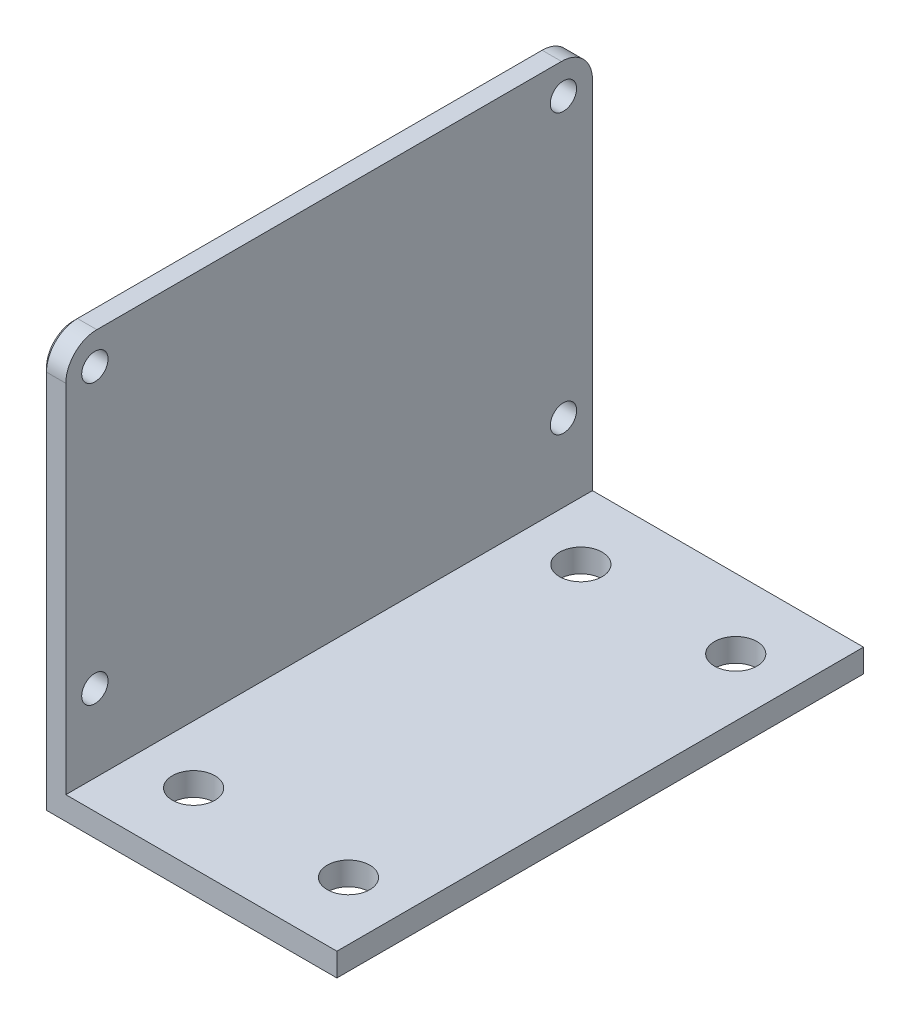
SolidWorks part; units mm, degrees
material "6061-T6 (SS)"
ref_plane "Front Plane" through (0, 0, 0) normal (0, 0, 1) x (1, 0, 0)
ref_plane "Top Plane" through (0, 0, 0) normal (0, 1, 0) x (1, 0, 0)
ref_plane "Right Plane" through (0, 0, 0) normal (1, 0, 0) x (0, 0, -1)
sketch "Sketch1" plane through (0, 0, 0) normal (0, 0, 1) x (1, 0, 0)
  line L0 (0, 0) -> (38, 0)
  line L1 (38, 0) -> (38, 3)
  line L2 (38, 3) -> (3, 3)
  line L3 (3, 3) -> (3, 53)
  line L4 (3, 53) -> (0, 53)
  line L5 (0, 53) -> (0, 0)
  dimension "D1" = 50
  dimension "D2" = 35
  dimension "D3" = 3
extrude "Boss-Extrude1" add sketch "Sketch1" along normal blind 68
sketch "Sketch2" plane through (3, 0, 0) normal (1, 0, 0) x (0, 0, -1)
  line L0 (-34, 31) -> (-34, 53) construction
  line L1 (-64.25, 49) -> (-3.75, 49) construction
  line L2 (-64.25, 49) -> (-64.25, 13) construction
  line L3 (-64.25, 13) -> (-3.75, 13) construction
  line L4 (-3.75, 49) -> (-3.75, 13) construction
  line L5 (-64.25, 49) -> (-3.75, 13) construction
  line L6 (-64.25, 13) -> (-3.75, 49) construction
  line L7 (-68, 53) -> (0, 53) construction
  point P0 (-34, 31)
  dimension "D1" = 60.5
  dimension "D2" = 36
  dimension "D3" = 4
hole_wizard "M3 Clearance Hole1" positions "Sketch4" profile "Sketch3" hole size "M3" standard "ANSI Metric"
sketch "Sketch4" plane through (3, 0, 0) normal (1, 0, 0) x (0, 0, -1)
  point P0 (-64.25, 49)
  point P3 (-3.75, 49)
  point P6 (-3.75, 13)
  point P9 (-64.25, 13)
sketch "Sketch3" plane through (3, 49, 64.25) normal (0, 1, 0) x (0, 0, -1)
  line L0 (0, 0) -> (0, 6.0215)
  line L1 (0, 6.0215) -> (1.7, 5)
  line L2 (1.7, 5) -> (1.7, 0)
  line L5 (1.7, 0) -> (0, 0)
  line L10 (0, 6.0215) -> (-1.7, 5) construction
  line L11 (0, -6.35) -> (0, 107.95) construction
  dimension "Hole Dia." = 3.4
  dimension "Hole Depth" = 5
  dimension "Drill Angle" = 118
sketch "Sketch5" plane through (0, 3, 0) normal (0, 1, 0) x (1, 0, 0)
  line L0 (20.5, 0) -> (20.5, -68) construction
  line L1 (38, 0) -> (3, 0) construction
  line L2 (38, -68) -> (3, -68) construction
  line L3 (3, -34) -> (38, -34) construction
  line L4 (3, -68) -> (3, 0) construction
  line L5 (38, -68) -> (38, 0) construction
  line L7 (10.5, -59) -> (30.5, -59) construction
  line L8 (10.5, -59) -> (10.5, -9) construction
  line L9 (10.5, -9) -> (30.5, -9) construction
  line L10 (30.5, -59) -> (30.5, -9) construction
  line L11 (10.5, -59) -> (30.5, -9) construction
  line L12 (10.5, -9) -> (30.5, -59) construction
  point P12 (20.5, -34)
  dimension "D1" = 20
  dimension "D2" = 50
hole_wizard "M5 Clearance Hole1" positions "Sketch7" profile "Sketch6" hole size "M5" standard "ANSI Metric"
sketch "Sketch7" plane through (0, 3, 0) normal (0, 1, 0) x (1, 0, 0)
  point P0 (30.5, -59)
  point P3 (10.5, -59)
  point P6 (10.5, -9)
  point P9 (30.5, -9)
sketch "Sketch6" plane through (30.5, 3, 59) normal (1, 0, 0) x (0, 0, 1)
  line L0 (0, 0) -> (0, 6.6524)
  line L1 (0, 6.6524) -> (2.75, 5)
  line L2 (2.75, 5) -> (2.75, 0)
  line L5 (2.75, 0) -> (0, 0)
  line L10 (0, 6.6524) -> (-2.75, 5) construction
  line L11 (0, -6.35) -> (0, 107.95) construction
  dimension "Hole Dia." = 5.5
  dimension "Hole Depth" = 5
  dimension "Drill Angle" = 118
fillet "Fillet1" radius 4 2 edges at (1.5, 53, 68) (1.5, 53, 0)
chamfer "Chamfer1" distance 0.5 angle 45 5 edges at (0, 24.5, 68) (0, 51.8284, 66.8284) (0, 53, 34) (0, 51.8284, 1.1716) (0, 24.5, 0)
